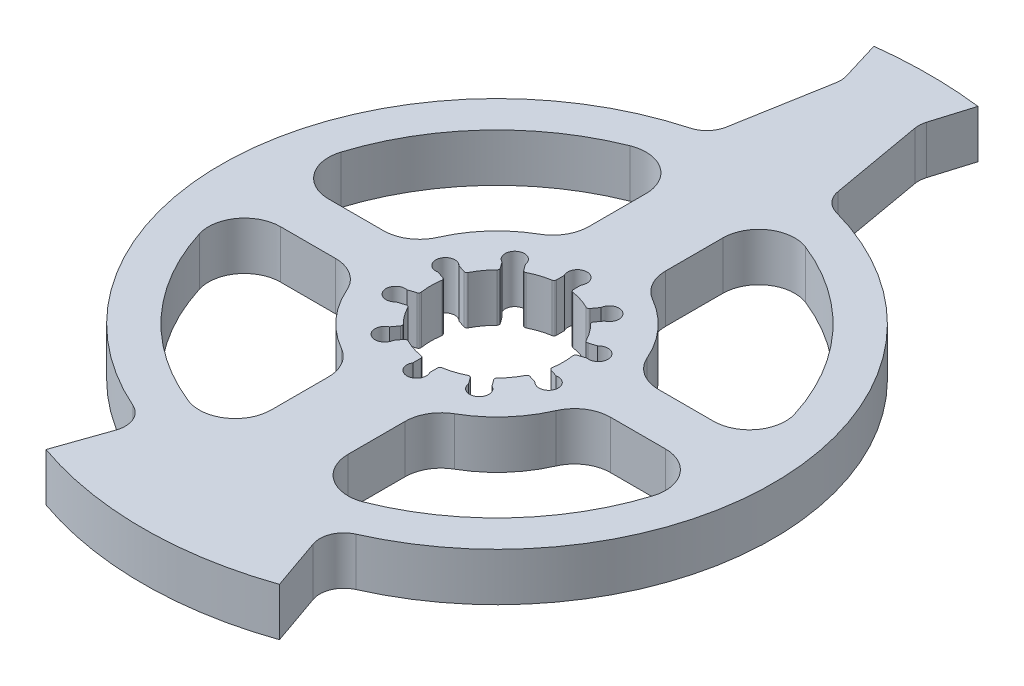
SolidWorks part; units mm, degrees
material "AISI Type A2 Tool Steel"
ref_plane "Front Plane" through (0, 0, 0) normal (0, 0, 1) x (1, 0, 0)
ref_plane "Top Plane" through (0, 0, 0) normal (0, 1, 0) x (1, 0, 0)
ref_plane "Right Plane" through (0, 0, 0) normal (1, 0, 0) x (0, 0, -1)
other "Center of Mass"
other "Bounding Box"
ref_plane "Default Plane" through (0, 2.286, 19.05) normal (0, -1, 0) x (-1, 0, 0)
sketch "Sketch1" plane through (0, 0, 0) normal (0, 1, 0) x (1, 0, 0)
  circle A0 centre (0, 0) radius 114.3 construction
  circle A1 centre (0, 0) radius 73.025
  circle A2 centre (0, 0) radius 17.4625
  dimension "D1" = 228.6
  dimension "D2" = 146.05
  dimension "D3" = 34.925
extrude "Boss-Extrude1" add sketch "Sketch1" along normal mid plane 12.7
sketch "Sketch2" plane through (0, 6.35, 0) normal (0, 1, 0) x (1, 0, 0)
  line L0 (-10.16, 101.6) -> (-15.4916, 71.3629)
  line L1 (15.4916, 71.3629) -> (10.16, 101.6)
  line L2 (10.16, 101.6) -> (13.77, 113.4675)
  line L3 (-10.16, 101.6) -> (-13.77, 113.4675)
  line L4 (0, 0) -> (0, 114.3) construction
  line L5 (-10.16, 101.6) -> (0, 101.6) construction
  line L6 (0, 101.6) -> (10.16, 101.6) construction
  line L7 (-13.77, 113.4675) -> (0, 0) construction
  circle A0 centre (0, 0) radius 114.3 construction
  circle A1 centre (0, 0) radius 114.3 construction
  arc A2 (-13.77, 113.4675) -> (13.77, 113.4675) centre (0, 0) cw
  circle A5 centre (0, 0) radius 73.025
  arc A6 (15.4916, 71.3629) -> (-15.4916, 71.3629) centre (0, 0) ccw
  arc A7 (-15.4916, 71.3629) -> (15.4916, 71.3629) centre (0, 0) ccw construction
  dimension "D3" = 10
  dimension "D4" = 12.7
  dimension "D5" = 10
  dimension "D6" = 10.16
  dimension "D2" = 0
extrude "Boss-Extrude2" add sketch "Sketch2" against normal through all
sketch "Sketch3" plane through (0, 6.35, 0) normal (0, 1, 0) x (1, 0, 0)
  line L0 (-30.8797, -88.4257) -> (-24.0757, -68.9421)
  line L1 (24.0757, -68.9421) -> (30.8797, -88.4257)
  line L2 (0, -73.025) -> (0, -93.6625) construction
  line L3 (0, -93.6625) -> (0, -114.3) construction
  line L4 (-24.0757, -68.9421) -> (0, 0) construction
  line L5 (0, 0) -> (24.0757, -68.9421) construction
  arc A0 (-30.8797, -88.4257) -> (30.8797, -88.4257) centre (0, 0) ccw
  circle A1 centre (0, 0) radius 73.025 construction
  circle A2 centre (0, 0) radius 114.3 construction
  arc A3 (-24.0757, -68.9421) -> (24.0757, -68.9421) centre (0, 0) ccw
  point P13 (0, -93.6625)
  dimension "D1" = 38.5
extrude "Boss-Extrude3" add sketch "Sketch3" against normal through all
sketch "Sketch4" plane through (0, 6.35, 0) normal (0, 1, 0) x (1, 0, 0)
  line L0 (0, 0) -> (-73.025, 0) construction
  line L1 (-62.5435, -6.35) -> (-29.4865, -6.35)
  line L4 (-10.16, -62.0386) -> (-10.16, -28.3998)
  line L8 (0, -93.6625) -> (0, 0) construction
  arc A0 (-10.16, -28.3998) -> (-29.4865, -6.35) centre (0, 0) cw
  arc A1 (-10.16, -62.0386) -> (-62.5435, -6.35) centre (0, 0) cw
  circle A2 centre (0, 0) radius 73.025 construction
  arc A5 (-30.8797, -88.4257) -> (30.8797, -88.4257) centre (0, 0) ccw construction
  arc A6 (-15.4916, 71.3629) -> (-24.0757, -68.9421) centre (0, 0) ccw construction
  circle A7 centre (0, 0) radius 17.4625 construction
  dimension "D1" = 10.16
  dimension "D2" = 12.7
  dimension "D3" = 10.16
  dimension "D4" = 6.35
extrude "Cut-Extrude1" cut sketch "Sketch4" against normal through all
mirror "Mirror1" about plane through (0, 0, 0) normal (1, 0, 0) of "Cut-Extrude1"
mirror "Mirror2" about plane through (0, 0, 0) normal (0, 0, 1) of "Mirror1"
sketch "Sketch5" plane through (0, 6.35, 0) normal (0, 1, 0) x (1, 0, 0)
  line L0 (0, 17.4625) -> (0, 21.2725) construction
  line L2 (-2.2225, 17.3205) -> (2.2225, 17.3205)
  line L3 (-2.2225, 17.3205) -> (-2.2225, 20.0168)
  line L5 (2.2225, 17.3205) -> (2.2225, 20.0168)
  arc A0 (2.2225, 20.0168) -> (-2.2225, 20.0168) centre (0, 21.2725) ccw
  circle A1 centre (0, 0) radius 17.4625 construction
  circle A2 centre (0, 21.2725) radius 4.5847 construction
  dimension "D2" = 5.1054
  dimension "D4" = 9.1694
  dimension "D1" = 3.81
  dimension "D3" = 4.445
extrude "Cut-Extrude2" cut sketch "Sketch5" against normal through all
pattern_circular "CirPattern1" count 10 over 360 about axis through (0, 6.35, 0) along (0, -1, 0) of "Cut-Extrude2"
sketch "Sketch6" plane through (0, 6.35, 0) normal (0, 1, 0) x (1, 0, 0)
  circle A0 centre (0, 0) radius 17.526
  arc A1 (-11.9788, 12.7062) -> (-15.786, 7.466) centre (0, 0) ccw construction
  dimension "D1" = 0.0635
extrude "Cut-Extrude3" cut sketch "Sketch6" against normal through all
fillet "Fillet1" radius 6.35 6 edges at (-24.0757, 0, 68.9421) (24.0757, 0, 68.9421) (15.4916, 0, -71.3629) (10.16, 0, -101.6) (-15.4916, 0, -71.3629) (-10.16, 0, -101.6)
fillet "Fillet4" radius 9.525 8 edges at (-10.16, 0, -62.0386) (-62.5435, 0, -6.35) (-62.5435, 0, 6.35) (-10.16, 0, 62.0386) (10.16, 0, 62.0386) (62.5435, 0, 6.35) (62.5435, 0, -6.35) (10.16, 0, -62.0386)
fillet "Fillet5" radius 9.525 8 edges at (-29.4865, 0, -6.35) (-10.16, 0, -28.3998) (10.16, 0, -28.3998) (29.4865, 0, -6.35) (10.16, 0, 28.3998) (29.4865, 0, 6.35) (-29.4865, 0, 6.35) (-10.16, 0, 28.3998)
fillet "Fillet6" radius 0.635 20 edges at (-12.0164, 0, -12.758) (-15.8469, 0, -7.4858) (-17.2204, 0, -3.2584) (-17.2204, 0, 3.2584) (-15.8469, 0, 7.4858) (-12.0164, 0, 12.758) (-8.4203, 0, 15.3707) (-2.2225, 0, 17.3845) (2.2225, 0, 17.3845) (8.4203, 0, 15.3707) (12.0164, 0, 12.758) (15.8469, 0, 7.4858) (17.2204, 0, 3.2584) (17.2204, 0, -3.2584) (15.8469, 0, -7.4858) (12.0164, 0, -12.758) (8.4203, 0, -15.3707) (2.2225, 0, -17.3845) (-2.2225, 0, -17.3845) (-8.4203, 0, -15.3707)
equation "\"Unit Measure\"= \"BoundingVolume\" / \"Thickness\"'in^2"
